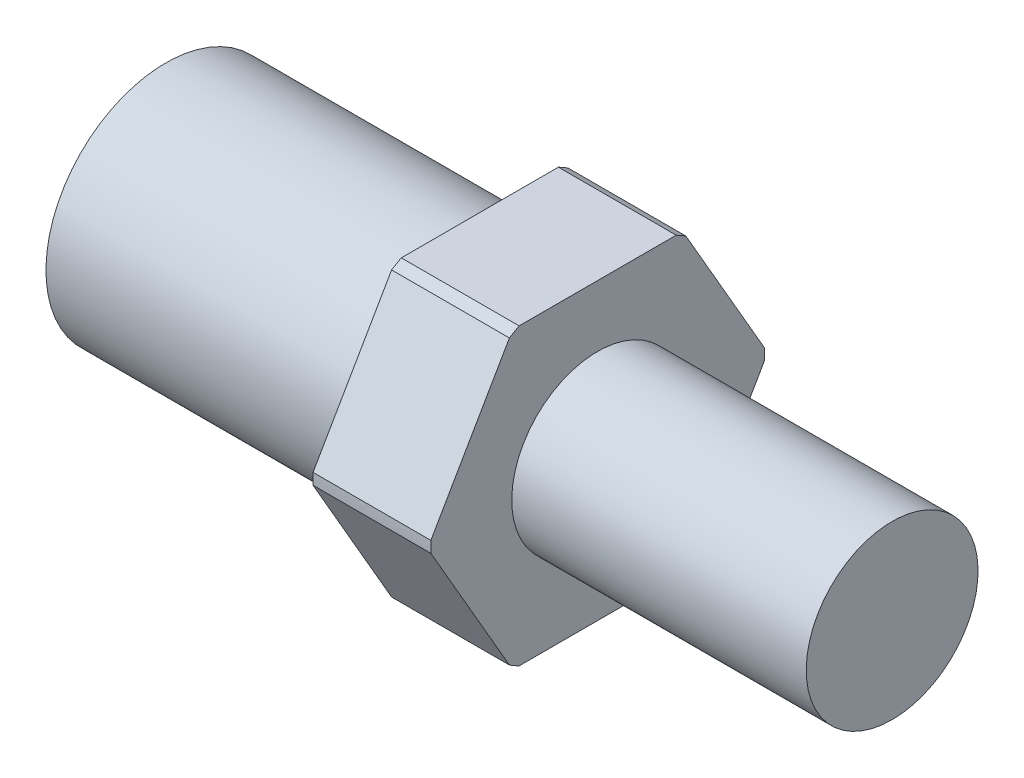
SolidWorks part; units mm, degrees
ref_plane "XY" through (0, 0, 0) normal (0, 0, 1) x (1, 0, 0)
ref_plane "XZ" through (0, 0, 0) normal (0, 1, 0) x (1, 0, 0)
ref_plane "YZ" through (0, 0, 0) normal (1, 0, 0) x (0, 0, -1)
ref_axis "X" through (-88.99, 0, 0) along (1, 0, 0)
ref_axis "Y" through (0, -55, 0) along (0, 1, 0)
ref_axis "Z" through (0, 0, 55) along (0, 0, -1)
sketch "Sketch1" plane through (0, 0, 0) normal (0, 0, 1) x (1, 0, 0)
  line L0 (0, 0) -> (0, 5.5562) construction
  line L1 (0, 10.795) -> (-7.62, 10.795)
  line L2 (-7.62, 10.795) -> (-7.62, 7.747)
  line L3 (-7.62, 7.747) -> (-27.94, 7.747)
  line L4 (-27.94, 7.747) -> (-27.94, 0)
  line L5 (-27.94, 0) -> (19.05, 0)
  line L6 (19.05, 0) -> (19.05, 5.5562)
  line L7 (19.05, 5.5562) -> (0, 5.5562)
  line L8 (0, 5.5562) -> (0, 10.795)
  dimension "D1" = 27.94
  dimension "D2" = 5.5562
  dimension "D3" = 7.747
  dimension "D4" = 10.795
  dimension "D5" = 7.62
  dimension "D6" = 19.05
revolve "Revolve1" add sketch "Sketch1" angle 360 about L5
sketch "Sketch2" plane through (-7.62, 0, 0) normal (-1, 0, 0) x (0, 0, 1)
  line L1 (-5.4993, 9.525) -> (-10.9985, 0)
  line L2 (-10.9985, 0) -> (-5.4993, -9.525)
  line L3 (-5.4993, -9.525) -> (5.4993, -9.525)
  line L4 (5.4993, -9.525) -> (10.9985, 0)
  line L5 (10.9985, 0) -> (5.4993, 9.525)
  line L6 (5.4993, 9.525) -> (-5.4993, 9.525)
  circle A0 centre (0, 0) radius 9.525 construction
  dimension "D1" = 19.05
extrude "Cut-Extrude1" cut sketch "Sketch2" against normal through all both and the other way through all flip side to cut
